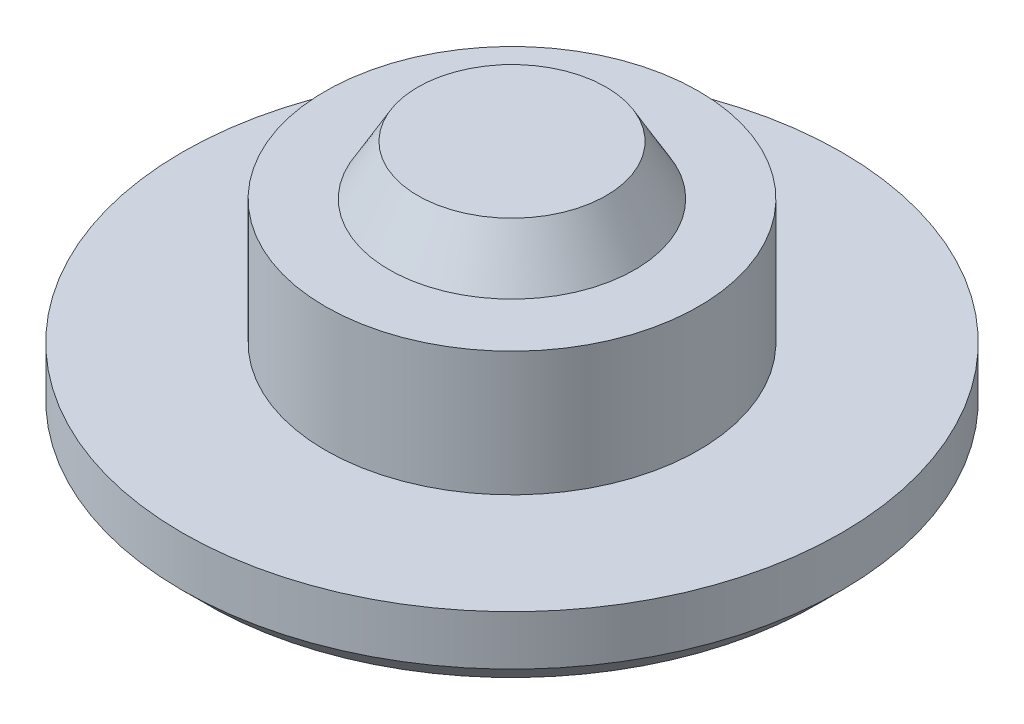
SolidWorks part; units mm, degrees
material "PET"
ref_plane "Front Plane" through (0, 0, 0) normal (0, 0, 1) x (1, 0, 0)
ref_plane "Top Plane" through (0, 0, 0) normal (0, 1, 0) x (1, 0, 0)
ref_plane "Right Plane" through (0, 0, 0) normal (1, 0, 0) x (0, 0, -1)
sketch "Sketch1" plane through (0, 0, 0) normal (0, 0, 1) x (1, 0, 0)
  line L0 (0, 0) -> (0, 40) construction
  line L1 (0, 40) -> (15.1312, 40)
  line L2 (15.1312, 40) -> (19.75, 32)
  line L3 (19.75, 32) -> (30, 32)
  line L4 (30, 32) -> (30, 12)
  line L5 (53, 12) -> (53, 4)
  line L6 (53, 4) -> (49, 0)
  line L7 (49, 0) -> (0, 0)
  line L8 (0, 0) -> (0, 40)
  line L9 (30, 12) -> (53, 12)
  dimension "D1" = 39.5
  dimension "D3" = 60
  dimension "D5" = 8
  dimension "D6" = 4
  dimension "D7" = 4
  dimension "D2" = 53
  dimension "D4" = 30
  dimension "D8" = 20
  dimension "D9" = 12
revolve "body" add sketch "Sketch1" angle 360 about L0
equation "\"paper_size\" = 600mm"
equation "\"cb_roll_d_outer\" = 80mm"
equation "\"cb_roll_d_inner\" = 78mm"
equation "\"attached_len\" = 70mm"
equation "\"helper_d\" = 86mm"
equation "\"outer_d\" = 106mm"
equation "\"spring_l_max\" = 25mm"
equation "\"spring_l_min\" = 10mm"
equation "\"cone_d_larger\" = 40mm"
equation "\"cone_angle\" = 60deg"
equation "\"D1@Sketch1\"=\"cone_d_larger\" - 0.5"
equation "\"D3@Sketch1\"=\"cone_angle\""
equation "\"D2@Sketch1\"=\"outer_d\" / 2"
